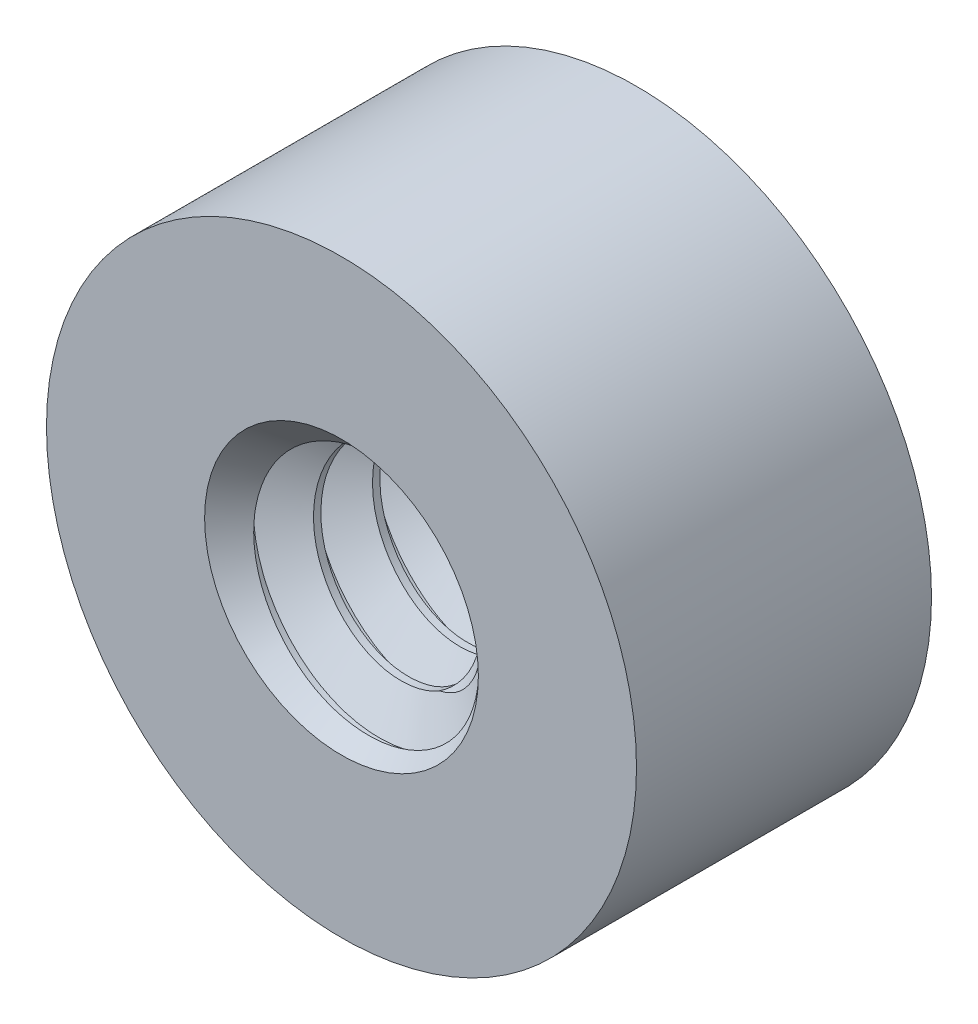
SolidWorks part; units mm, degrees
ref_plane "Front Plane" through (0, 0, 0) normal (0, 0, 1) x (1, 0, 0)
ref_plane "Top Plane" through (0, 0, 0) normal (0, 1, 0) x (1, 0, 0)
ref_plane "Right Plane" through (0, 0, 0) normal (1, 0, 0) x (0, 0, -1)
sketch "Sketch3" plane through (0, 0, 0) normal (1, 0, 0) x (0, 0, -1)
  line L0 (-1.5875, 0) -> (1.5875, 0) construction
  line L1 (0, 3.175) -> (0, -3.175) construction
  line L2 (-1.5875, 1.4224) -> (-1.5875, -1.4224) construction
  point P2 (-9.525, 0)
  point P3 (9.525, 0)
  dimension "Length" = 3.175
  dimension "Min Thread Length" = 11.1125
  dimension "D1" = 11.1125
  dimension "Thread Dia" = 2.8448
  dimension "OD" = 6.35
sketch "Sketch1" plane through (0, 0, 0) normal (0, 0, 1) x (1, 0, 0)
  circle A1 centre (0, 0) radius 1.4224
  circle A2 centre (0, 0) radius 3.175
extrude "Extrude1" add sketch "Sketch1" along normal up to vertex (1.5875 mm away) and the other way up to vertex (1.5875 mm away) up to point (0, 0, 1.5875) other way up to point (0, 0, -1.5875)
sketch "Sketch11" plane through (0, 0, -1.5875) normal (0, 0, -1) x (-1, 0, 0)
  circle A0 centre (0, 0) radius 1.4224 construction
  circle A1 centre (0, 0) radius 1.4224
curve "Helix/Spiral1" pitch 0.635 height 3.81 radius 1.4224 centre (0, 0, -1.5875) axis (0, 0, 1) start towards (0, 1, 0) parameters "Pitch"=0.635
sketch "Sketch12" plane through (0, 0, 0) normal (1, 0, 0) x (0, 0, -1)
  line L0 (2.1431, 1.4224) -> (1.5875, 1.4224)
  line L1 (2.1431, 1.4224) -> (1.905, 1.01)
  line L2 (1.905, 1.01) -> (1.8256, 1.01)
  line L3 (1.8256, 1.01) -> (1.5875, 1.4224)
  line L4 (1.8653, 1.01) -> (1.8653, 1.4224) construction
  line L5 (2.0241, 1.2162) -> (1.7066, 1.2162) construction
  dimension "D1" = 0.0794
  dimension "D2" = 0.3175
  dimension "D3" = 60
sweep "Sweep1" add profiles "Sketch12" path "Helix/Spiral1"
sketch "Sketch6" plane through (0, 0, -1.5875) normal (0, 0, -1) x (-1, 0, 0)
  circle A1 centre (0, 0) radius 3.175
  circle A2 centre (0, 0) radius 3.175
  dimension "D1" = 0
extrude "Extrude2" cut sketch "Sketch6" along normal through all
sketch "Sketch7" plane through (0, 0, -1.5875) normal (0, 0, -1) x (-1, 0, 0)
  circle A2 centre (0, 0) radius 1.4732
  circle A3 centre (0, 0) radius 1.4732
  dimension "D1" = 0.0508
extrude "Extrude3" cut sketch "Sketch7" against normal through all draft 43
mirror "Mirror1" about plane through (0, 0, 0) normal (0, 0, 1) of "Extrude2", "Extrude3"
sketch "Sketch9" [suppressed] plane through (0, 0, 0) normal (1, 0, 0) x (0, 0, -1)
  line L1 (-20.6375, 2.1336) -> (20.6375, 2.1336)
  line L2 (-20.6375, 2.1336) -> (-20.6375, 0)
  line L3 (-20.6375, 0) -> (20.6375, 0)
  line L4 (20.6375, 2.1336) -> (20.6375, 0)
  line L7 (-31.75, 0) -> (31.75, 0) construction
revolve "Revolve" [suppressed] add sketch "Sketch9" angle 360 about L0
sketch "Sketch10" [suppressed] plane through (0, 0, 0) normal (1, 0, 0) x (0, 0, -1)
  line L0 (31.75, 2.0828) -> (20.6375, 2.0828)
  line L1 (-31.75, 2.0828) -> (-20.6375, 2.0828)
  line L2 (20.6375, 2.0828) -> (20.6375, -2.0828)
  line L3 (-31.75, -2.1336) -> (-20.6375, -2.1336)
  line L4 (-20.6375, 2.0828) -> (-20.6375, -2.1336)
  line L5 (20.6375, -2.0828) -> (31.75, -2.0828)
equation "\"D1@Sketch3\" = \"Min Thread Length@Sketch3\""
equation "\"D3@Helix/Spiral1\" = \"Length@Sketch3\"+\"Pitch@Helix/Spiral1\""
equation "\"D1@Sketch12\" = \"Pitch@Helix/Spiral1\"*.125"
equation "\"D2@Sketch12\" = \"Pitch@Helix/Spiral1\"*.5"
